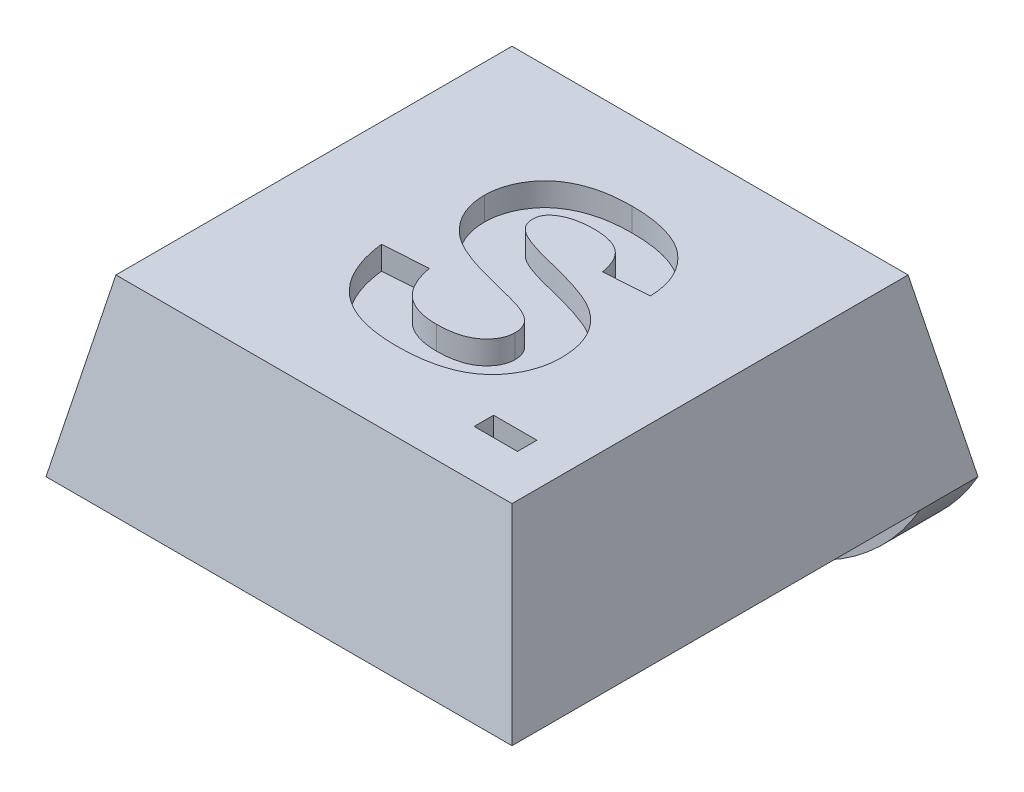
SolidWorks part; units mm, degrees
ref_plane "Front Plane" through (0, 0, 0) normal (0, 0, 1) x (1, 0, 0)
ref_plane "Top Plane" through (0, 0, 0) normal (0, 1, 0) x (1, 0, 0)
ref_plane "Right Plane" through (0, 0, 0) normal (1, 0, 0) x (0, 0, -1)
sketch "Sketch1" plane through (0, 0, 0) normal (0, 1, 0) x (1, 0, 0)
  line L1 (0, 0) -> (8, 0)
  line L2 (0, 0) -> (0, 8)
  line L3 (0, 8) -> (8, 8)
  line L4 (8, 0) -> (8, 8)
  dimension "D1" = 8
  dimension "D2" = 8
extrude "Boss-Extrude1" add sketch "Sketch1" along normal blind 3
sketch "Sketch2" plane through (0, 0, 0) normal (0, 0, 1) x (1, 0, 0)
  line L0 (0, 0) -> (0.6, 3)
  line L1 (0, 3) -> (8, 3) construction
  line L2 (0.6, 3) -> (0, 3)
  line L3 (0, 3) -> (0, 0)
  line L4 (8, 0) -> (7.4, 3)
  line L5 (7.4, 3) -> (8, 3)
  line L6 (8, 3) -> (8, 0)
  dimension "D1" = 0.6
  dimension "D2" = 0.6
extrude "Cut-Extrude1" cut sketch "Sketch2" against normal through all both and the other way through all
sketch "Sketch3" plane through (0, 0, 0) normal (1, 0, 0) x (0, 0, -1)
  line L0 (0, 0) -> (0.6, 3)
  line L1 (8, 3) -> (0, 3) construction
  line L2 (0.6, 3) -> (0, 3)
  line L3 (0, 3) -> (0, 0)
  line L4 (8, 3) -> (7.4, 3)
  line L5 (7.4, 3) -> (8, 0)
  line L6 (8, 3) -> (8, 0)
  dimension "D1" = 0.6
  dimension "D2" = 0.6
extrude "Cut-Extrude2" cut sketch "Sketch3" along normal blind 11
sketch "Sketch4" plane through (0, 0, 0) normal (0, -1, 0) x (1, 0, 0)
  line L0 (8, 0) -> (8, -8) construction
  line L3 (0, 0) -> (8, 0) construction
  circle A0 centre (4, -3.75) radius 1.75
  dimension "D1" = 3.5
  dimension "D2" = 4
  dimension "D3" = 3.75
extrude "Cut-Extrude3" cut sketch "Sketch4" against normal blind 0.4
sketch "Sketch5" plane through (0, 0, 0) normal (0, -1, 0) x (1, 0, 0)
  line L0 (8, 0) -> (8, -8) construction
  line L1 (0, -8) -> (8, -8)
  line L2 (0, -8) -> (0, -7)
  line L3 (0, -7) -> (8, -7)
  line L4 (8, -8) -> (8, -7)
  dimension "D1" = 1
extrude "Boss-Extrude2" add sketch "Sketch5" along normal blind 2
fillet "Fillet1" radius 4 2 edges at (8, -2, -7.5) (0, -2, -7.5)
sketch "Sketch6" plane through (0, 3, 0) normal (0, 1, 0) x (1, 0, 0)
  text T0 "S" font "Arial" height 4
extrude "Cut-Extrude4" cut sketch "Sketch6" against normal blind 0.4
sketch "Sketch7" plane through (0, 3, 0) normal (0, 1, 0) x (1, 0, 0)
  text T0 "-" font "Arial" height 2
extrude "Cut-Extrude5" cut sketch "Sketch7" against normal blind 0.5
